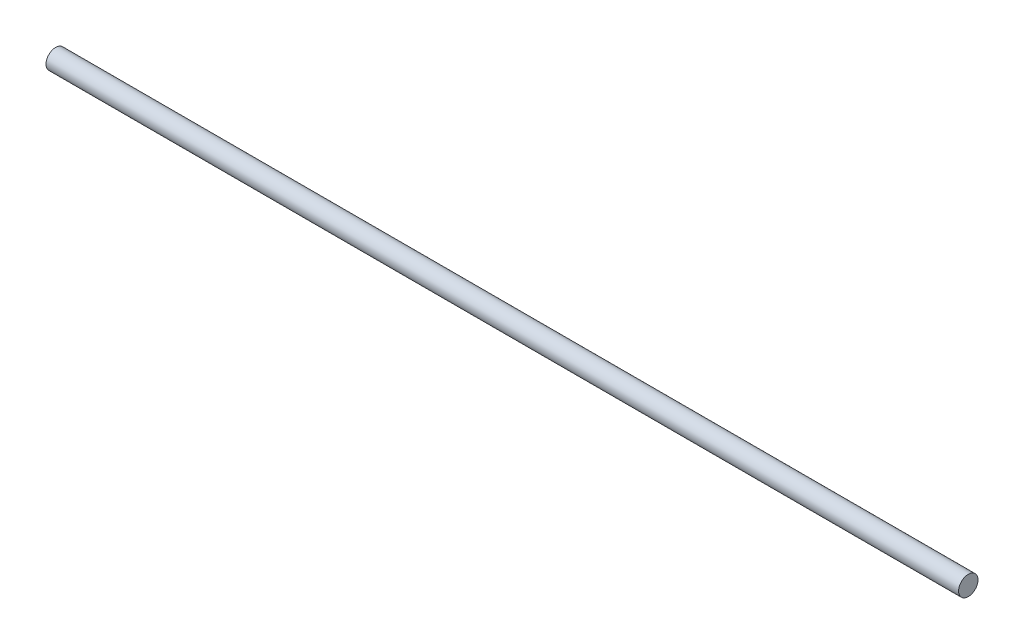
SolidWorks part; units mm, degrees
ref_plane "Front Plane" through (0, 0, 0) normal (0, 0, 1) x (1, 0, 0)
ref_plane "Top Plane" through (0, 0, 0) normal (0, 1, 0) x (1, 0, 0)
ref_plane "Right Plane" through (0, 0, 0) normal (1, 0, 0) x (0, 0, -1)
sketch "Sketch1" plane through (0, 0, 0) normal (1, 0, 0) x (0, 0, -1)
  circle A0 centre (0, 0) radius 3.175
  dimension "D1" = 6.35
extrude "Boss-Extrude1" add sketch "Sketch1" along normal blind 149.225 and the other way blind 149.225
ref_axis "Axis1" through (149.225, 0, 0) along (-1, 0, 0)
